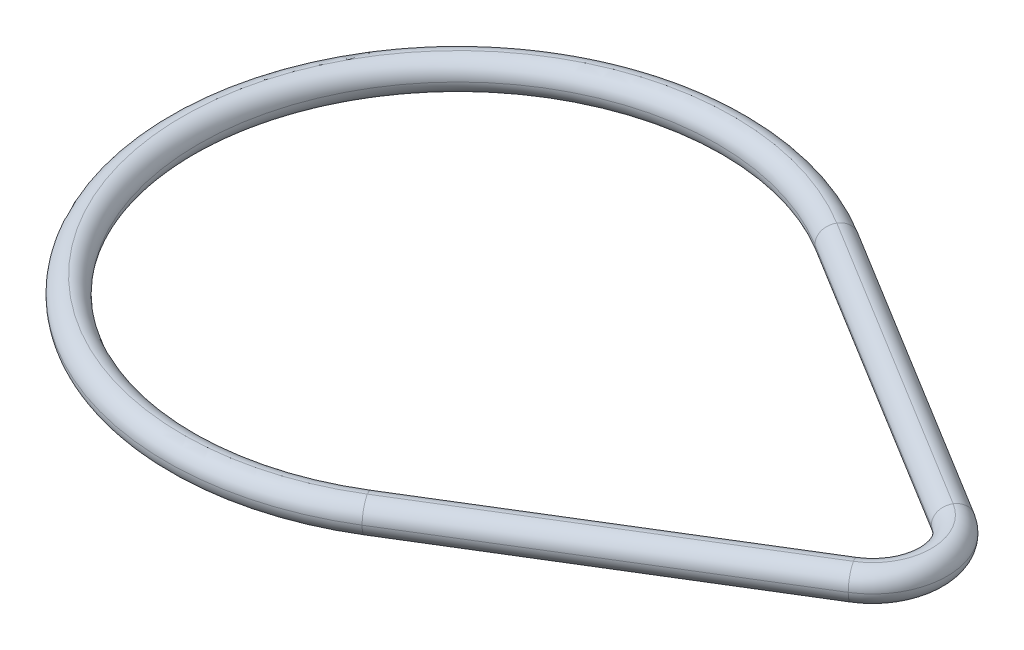
SolidWorks part; units mm, degrees
material "BUTYL"
ref_plane "Front Plane" through (0, 0, 0) normal (0, 0, 1) x (1, 0, 0)
ref_plane "Top Plane" through (0, 0, 0) normal (0, 1, 0) x (1, 0, 0)
ref_plane "Right Plane" through (0, 0, 0) normal (1, 0, 0) x (0, 0, -1)
sketch "Sketch1" plane through (0, 0, 0) normal (0, 1, 0) x (1, 0, 0)
  line L0 (6.3815, 10.3979) -> (20.5462, 1.7046)
  line L1 (20.5462, -1.7046) -> (6.3815, -10.3979)
  arc A0 (20.5462, 1.7046) -> (20.5462, -1.7046) centre (19.5, 0) cw
  arc A1 (6.3815, -10.3979) -> (6.3815, 10.3979) centre (0, 0) cw
  point P6 (0, 0)
  point P8 (0, 0)
  dimension "D1" = 19.5
  dimension "D2" = 2
  dimension "D3" = 12.2
extrude "Extrude-Thin1" add sketch "Sketch1" along normal mid plane 1.5 thin thin type one direction wall 1.5
fillet "Fillet1" radius 0.75 16 edges at (14.2485, 0.75, -7.3297) (23, 0.75, 0) (14.2485, 0.75, 7.3297) (14.2485, -0.75, -7.3297) (23, -0.75, 0) (14.2485, -0.75, 7.3297) (13.4638, 0.75, -6.0512) (21.5, 0.75, 0) (13.4638, 0.75, 6.0512) (13.4638, -0.75, -6.0512) (21.5, -0.75, 0) (13.4638, -0.75, 6.0512) (-13.7, 0.75, 0) (-13.7, -0.75, 0) (-12.2, 0.75, 0) (-12.2, -0.75, 0)
